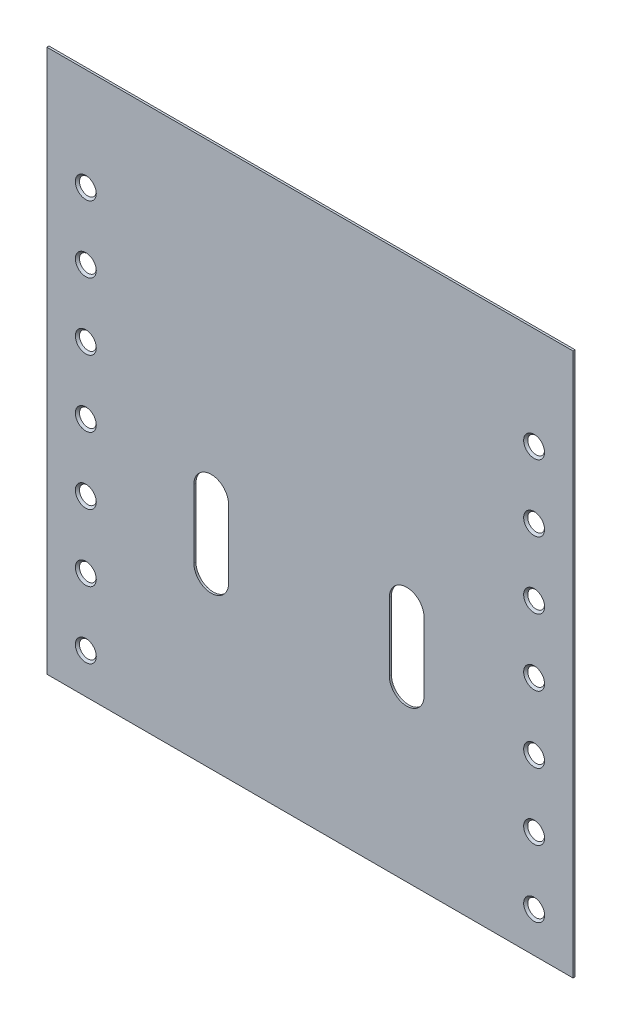
SolidWorks part; units mm, degrees
ref_plane "Front Plane" through (0, 0, 0) normal (0, 0, 1) x (1, 0, 0)
ref_plane "Top Plane" through (0, 0, 0) normal (0, 1, 0) x (1, 0, 0)
ref_plane "Right Plane" through (0, 0, 0) normal (1, 0, 0) x (0, 0, -1)
sketch "Sketch1" plane through (0, 0, 0) normal (0, 0, -1) x (1, 0, 0)
  line L1 (-203.2, 237) -> (-6.35, 237)
  line L2 (-203.2, 237) -> (-203.2, 33.8)
  line L3 (-203.2, 33.8) -> (-6.35, 33.8)
  line L4 (-6.35, 237) -> (-6.35, 33.8)
  dimension "D2" = 196.85
  dimension "D3" = 203.2
extrude "Boss-Extrude1" add sketch "Sketch1" along normal blind 0.7747
sketch "Sketch2" plane through (0, 0, -0.7747) normal (0, 0, -1) x (1, 0, 0)
  line L0 (-141.7213, 180) -> (-141.7213, 141.5) construction
  line L1 (-6.35, 237) -> (-203.2, 237) construction
  line L2 (-141.7213, 180) -> (-141.7213, 237) construction
  line L3 (-141.7213, 173.5) -> (-141.7213, 148) construction
  line L6 (-135.2213, 173.5) -> (-135.2213, 148)
  line L7 (-148.2213, 173.5) -> (-148.2213, 148)
  line L8 (-141.7213, 160.75) -> (-203.2, 160.75) construction
  line L9 (-203.2, 237) -> (-203.2, 33.8) construction
  line L10 (-68.5693, 180) -> (-68.5693, 141.5) construction
  line L11 (-68.5693, 180) -> (-68.5693, 237) construction
  line L12 (-68.5693, 173.5) -> (-68.5693, 148) construction
  line L15 (-141.7213, 160.75) -> (-68.5693, 160.75) construction
  line L16 (-62.0693, 173.5) -> (-62.0693, 148)
  line L17 (-75.0693, 173.5) -> (-75.0693, 148)
  arc A2 (-135.2213, 173.5) -> (-148.2213, 173.5) centre (-141.7213, 173.5) ccw
  arc A3 (-148.2213, 148) -> (-135.2213, 148) centre (-141.7213, 148) ccw
  arc A6 (-62.0693, 173.5) -> (-75.0693, 173.5) centre (-68.5693, 173.5) ccw
  arc A7 (-75.0693, 148) -> (-62.0693, 148) centre (-68.5693, 148) ccw
  point P5 (-141.7213, 160.75)
  point P18 (-68.5693, 160.75)
  dimension "D4" = 6.5
  dimension "D6" = 57
  dimension "D5" = 6.5
  dimension "D1" = 73.152
  dimension "D2" = 57
  dimension "D3" = 38.5
  dimension "D8" = 38.5
extrude "Cut-Extrude7" cut sketch "Sketch2" against normal through all
ref_plane "Plane1" through (-104.775, 0, 0) normal (1, 0, 0) x (0, 0, -1)
sketch "Sketch4" plane through (0, 0, 0) normal (0, 0, 1) x (1, 0, 0)
  line L0 (-203.2, -33.8) -> (-6.35, -33.8) construction
  line L1 (-6.35, -33.8) -> (-203.2, -33.8)
  line L2 (-6.35, -33.8) -> (-6.35, -34.4096)
  line L3 (-6.35, -34.4096) -> (-203.2, -34.4096)
  line L4 (-203.2, -33.8) -> (-203.2, -34.4096)
  line L5 (-6.35, -237) -> (-6.35, 2) construction
  line L6 (-203.2, 2) -> (-203.2, -237) construction
  dimension "D1" = 0.6096
extrude "Boss-Extrude2" add sketch "Sketch4" along normal blind 12
sketch "Sketch8" plane through (0, 0, -0.7747) normal (0, 0, -1) x (-1, 0, 0)
  circle A0 centre (185.47, -222) radius 3.75
  circle A1 centre (185.47, -197) radius 3.75
  circle A2 centre (185.47, -172) radius 3.75
  circle A3 centre (185.47, -147) radius 3.75
  circle A4 centre (185.47, -122) radius 3.75
  circle A5 centre (185.47, -97) radius 3.75
  dimension "D1" = 7.5
sketch "Sketch13" plane through (0, 0, 12) normal (0, 0, 1) x (1, 0, 0)
  line L1 (-6.35, -34.4096) -> (-203.2, -34.4096)
  line L2 (-6.35, -34.4096) -> (-6.35, -33.8)
  line L3 (-6.35, -33.8) -> (-203.2, -33.8)
  line L4 (-203.2, -34.4096) -> (-203.2, -33.8)
sketch "Sketch14" plane through (0, 0, 0) normal (0, 0, 1) x (1, 0, 0)
  line L0 (-6.35, -34.4096) -> (-6.35, -237) construction
  line L1 (-6.35, -59.904) -> (-203.2, -59.904)
  line L2 (-6.35, -59.904) -> (-6.35, -47.966)
  line L3 (-6.35, -47.966) -> (-203.2, -47.966)
  line L4 (-203.2, -59.904) -> (-203.2, -47.966)
  line L5 (-203.2, -237) -> (-203.2, -34.4096) construction
  dimension "D1" = 11.938
extrude "Boss-Extrude3" add sketch "Sketch14" against normal up to surface (0.7747 mm away) up to face at (-141.7213, -160.75, -0.7747)
extrude "Cut-Extrude9" cut sketch "Sketch13" against normal up to surface (12 mm away) up to face at (-68.5693, -160.75, 0)
hole_wizard "CSK for M3 Flat Head Machine Screw3" positions "Sketch15" profile "Sketch16" countersink size "M3" standard "ANSI Metric" end condition through all
sketch "Sketch15" plane through (0, 0, 0) normal (0, 0, 1) x (1, 0, 0)
  point P18 (-188.645, -72)
  point P21 (-188.645, -222)
  point P24 (-188.645, -197)
  point P27 (-188.645, -172)
  point P30 (-188.645, -147)
  point P33 (-188.645, -122)
  point P36 (-188.645, -97)
  point P39 (-188.645, -72)
sketch "Sketch16" plane through (-188.645, -72, 0) normal (1, 0, 0) x (0, -1, 0)
  line L0 (0, 0) -> (0, 0.7747)
  line L1 (0, 0.7747) -> (1.7, 0.7747)
  line L2 (1.7, 0.7747) -> (1.7, 2.212)
  line L3 (1.7, 2.212) -> (3.912, 0)
  line L5 (3.912, 0) -> (0, 0)
  line L6 (-1.7, 2.212) -> (-3.912, 0) construction
  line L11 (0, -6.35) -> (0, 107.95) construction
  dimension "Thru Hole Dia." = 3.4
  dimension "Thru Hole Depth" = 0.7747
  dimension "Near C'Sink Dia." = 7.824
  dimension "Near C'Sink Angle" = 90
ref_plane "Plane2" through (-104.775, 0, 0) normal (-1, 0, 0) x (0, 0, 1)
mirror "Mirror1" about plane through (-104.775, 0, 0) normal (-1, 0, 0) of "CSK for M3 Flat Head Machine Screw3"
